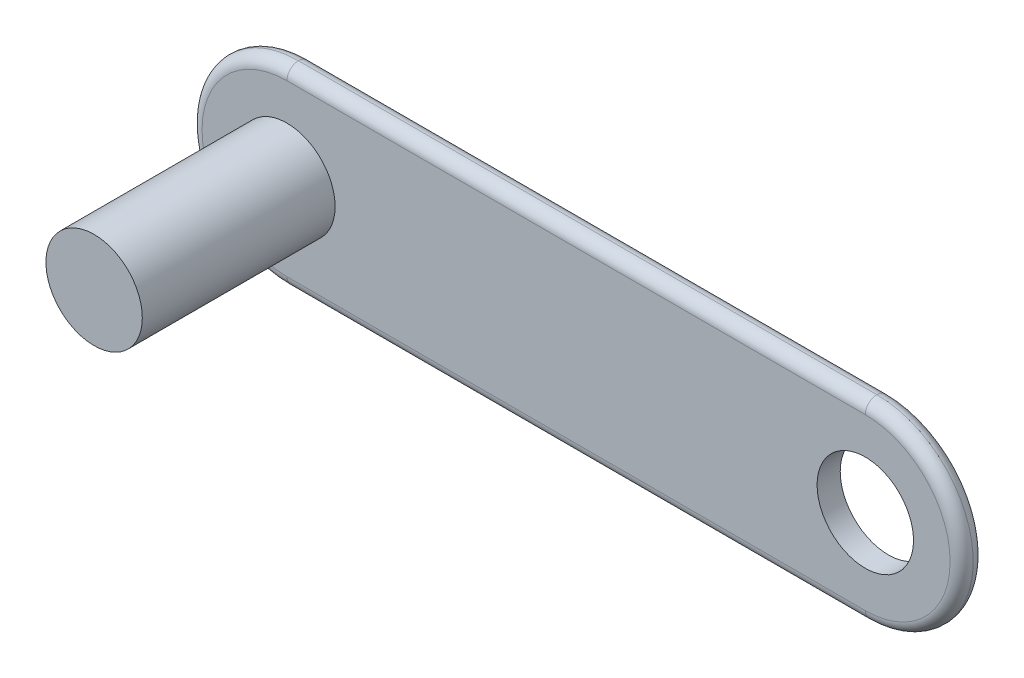
SolidWorks part; units mm, degrees
ref_plane "Front Plane" through (0, 0, 0) normal (0, 0, 1) x (1, 0, 0)
ref_plane "Top Plane" through (0, 0, 0) normal (0, 1, 0) x (1, 0, 0)
ref_plane "Right Plane" through (0, 0, 0) normal (1, 0, 0) x (0, 0, -1)
sketch "Sketch1" plane through (0, 0, 0) normal (0, 0, 1) x (1, 0, 0)
  line L0 (0, 0) -> (76.2, 0) construction
  line L1 (0, 12.7) -> (76.2, 12.7)
  line L2 (0, -12.7) -> (76.2, -12.7)
  arc A0 (0, 12.7) -> (0, -12.7) centre (0, 0) ccw
  arc A1 (76.2, -12.7) -> (76.2, 12.7) centre (76.2, 0) ccw
  point P3 (38.1, 0)
  dimension "D1" = 12.7
  dimension "D2" = 76.2
extrude "Boss-Extrude1" add sketch "Sketch1" along normal mid plane 3.048
sketch "Sketch2" plane through (0, 0, 0) normal (0, 0, 1) x (1, 0, 0)
  line L2 (0, -12.7) -> (76.2, -12.7)
  line L3 (76.2, 12.7) -> (0, 12.7)
  line L4 (0, -12.7) -> (76.2, -12.7)
  line L5 (76.2, 12.7) -> (0, 12.7)
  circle A0 centre (76.2, 0) radius 6.35
  arc A2 (0, 12.7) -> (0, -12.7) centre (0, 0) ccw
  arc A3 (76.2, -12.7) -> (76.2, 12.7) centre (76.2, 0) ccw
  arc A4 (0, 12.7) -> (0, -12.7) centre (0, 0) ccw
  arc A5 (76.2, -12.7) -> (76.2, 12.7) centre (76.2, 0) ccw
  dimension "D2" = 12.7
  dimension "D1" = 0
extrude "Cut-Extrude1" cut sketch "Sketch2" against normal through all and the other way blind 3.048 contours A0
sketch "Sketch3" plane through (0, 0, 0) normal (0, 0, 1) x (1, 0, 0)
  line L2 (0, -12.7) -> (76.2, -12.7)
  line L3 (76.2, 12.7) -> (0, 12.7)
  line L4 (0, -12.7) -> (76.2, -12.7)
  line L5 (76.2, 12.7) -> (0, 12.7)
  circle A0 centre (0, 0) radius 6.35
  arc A2 (0, 12.7) -> (0, -12.7) centre (0, 0) ccw
  arc A3 (76.2, -12.7) -> (76.2, 12.7) centre (76.2, 0) ccw
  arc A4 (0, 12.7) -> (0, -12.7) centre (0, 0) ccw
  arc A5 (76.2, -12.7) -> (76.2, 12.7) centre (76.2, 0) ccw
  dimension "D2" = 12.7
  dimension "D1" = 0
sketch "Sketch4" plane through (0, 0, 1.524) normal (0, 0, 1) x (1, 0, 0)
  circle A0 centre (0, 0) radius 6.35 construction
  circle A1 centre (0, 0) radius 6.35
extrude "Boss-Extrude3" add sketch "Sketch4" along normal blind 25.4
fillet "Fillet1" radius 1.524 8 edges at (88.9, 0, 1.524) (38.1, -12.7, 1.524) (-12.7, 0, 1.524) (88.9, 0, -1.524) (38.1, -12.7, -1.524) (-12.7, 0, -1.524) (38.1, 12.7, 1.524) (38.1, 12.7, -1.524)
